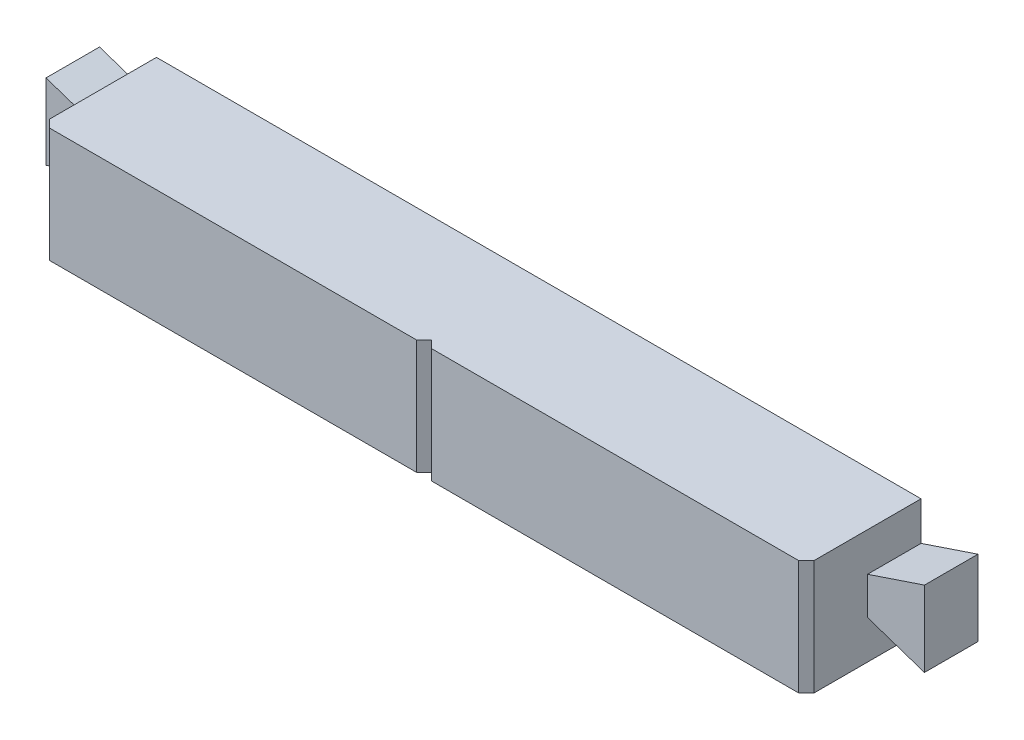
SolidWorks part; units mm, degrees
ref_plane "Front Plane" through (0, 0, 0) normal (0, 0, 1) x (1, 0, 0)
ref_plane "Top Plane" through (0, 0, 0) normal (0, 1, 0) x (1, 0, 0)
ref_plane "Right Plane" through (0, 0, 0) normal (1, 0, 0) x (0, 0, -1)
sketch "Sketch1" plane through (0, 0, 0) normal (0, 0, 1) x (1, 0, 0)
  line L1 (-50, -7.5) -> (50, -7.5)
  line L2 (-50, -7.5) -> (-50, 7.5)
  line L3 (-50, 7.5) -> (50, 7.5)
  line L4 (50, -7.5) -> (50, 7.5)
  line L5 (-50, -7.5) -> (50, 7.5) construction
  line L6 (-50, 7.5) -> (50, -7.5) construction
  point P0 (0, 0)
  dimension "D1" = 100
  dimension "D2" = 15
extrude "Body" add sketch "Sketch1" along normal blind 15
sketch "Sketch2" plane through (0, 0, 0) normal (0, 0, 1) x (1, 0, 0)
  line L0 (-50, 0) -> (50, 0) construction
  line L1 (-50, 7.5) -> (-50, -7.5) construction
  line L2 (50, -7.5) -> (50, 7.5) construction
  line L3 (-50, 0) -> (-50, 2.45)
  line L4 (-50, 2.45) -> (-57.45, 4.95)
  line L6 (-57.45, -4.95) -> (-50, -2.45)
  line L7 (-50, -2.45) -> (-50, 0)
  line L8 (-50, 0) -> (-63.3586, 0) construction
  line L9 (-57.45, 4.95) -> (-57.45, 0)
  line L10 (-57.45, 0) -> (-57.45, -4.95)
  line L11 (0, 7.5) -> (0, -7.5) construction
  line L12 (50, 7.5) -> (-50, 7.5) construction
  line L13 (-50, -7.5) -> (50, -7.5) construction
  line L14 (50, 0) -> (63.3586, 0) construction
  line L15 (57.45, 0) -> (57.45, -4.95)
  line L16 (57.45, 4.95) -> (57.45, 0)
  line L17 (50, -2.45) -> (50, 0)
  line L18 (57.45, -4.95) -> (50, -2.45)
  line L19 (50, 2.45) -> (57.45, 4.95)
  line L20 (50, 0) -> (50, 2.45)
  dimension "D1" = 2.45
  dimension "D2" = 2.45
  dimension "D3" = 4.95
  dimension "D4" = 4.95
  dimension "D5" = 7.45
extrude "Click" add sketch "Sketch2" along normal blind 7
chamfer "Click Chamfer" distance 1 angle 45 2 edges at (-50, 0, 15) (50, 0, 15)
sketch "Sketch3" plane through (0, -7.5, 0) normal (0, -1, 0) x (1, 0, 0)
  line L0 (-50, 5.75) -> (50, 5.75) construction
  line L1 (-50, 7) -> (-50, 0) construction
  line L2 (50, 14) -> (50, 0) construction
  line L3 (-50, 0) -> (50, 0) construction
  line L4 (0, 15) -> (0, 0) construction
  line L5 (-49, 15) -> (49, 15) construction
  circle A0 centre (-25, 5.75) radius 2.5
  circle A1 centre (25, 5.75) radius 2.5
  dimension "D2" = 5
  dimension "D3" = 5
  dimension "D1" = 5.75
  dimension "D4" = 25
  dimension "D5" = 25
extrude "LED Hole" cut sketch "Sketch3" against normal blind 8
sketch "Sketch4" plane through (0, 0, 15) normal (0, 0, 1) x (1, 0, 0)
  line L0 (0, 7.5) -> (0, -7.5) construction
  line L1 (49, 7.5) -> (-49, 7.5) construction
  line L2 (-49, -7.5) -> (49, -7.5) construction
  line L4 (-1, -7.5) -> (1, -7.5)
  line L5 (-1, -7.5) -> (-1, 7.5)
  line L6 (-1, 7.5) -> (1, 7.5)
  line L7 (1, -7.5) -> (1, 7.5)
  line L8 (-1, -7.5) -> (1, 7.5) construction
  line L9 (-1, 7.5) -> (1, -7.5) construction
  point P6 (0, 0)
  dimension "D1" = 2
extrude "FieldMark" cut sketch "Sketch4" against normal blind 2
chamfer "FieldMark Chamfer" distance 2 angle 45 2 edges at (1, 0, 13) (-1, 0, 13)
ref_plane "Plane1" through (0, -6.5, 0) normal (0, -1, 0) x (-1, 0, 0)
sketch "Sketch6" plane through (0, -7.5, 0) normal (0, -1, 0) x (1, 0, 0)
  line L0 (-25, 5.75) -> (25, 5.75) construction
  line L1 (-25, 5.75) -> (-42.5109, 5.75) construction
  line L2 (25, 5.75) -> (43.3201, 5.75) construction
  line L4 (34.5, -1.75) -> (35.5, -1.75)
  line L5 (34.5, -1.75) -> (34.5, 13.25)
  line L6 (34.5, 13.25) -> (35.5, 13.25)
  line L7 (35.5, -1.75) -> (35.5, 13.25)
  line L8 (34.5, -1.75) -> (35.5, 13.25) construction
  line L9 (34.5, 13.25) -> (35.5, -1.75) construction
  line L10 (14.5, -1.75) -> (15.5, -1.75)
  line L11 (14.5, -1.75) -> (14.5, 13.25)
  line L12 (14.5, 13.25) -> (15.5, 13.25)
  line L13 (15.5, -1.75) -> (15.5, 13.25)
  line L14 (14.5, -1.75) -> (15.5, 13.25) construction
  line L15 (14.5, 13.25) -> (15.5, -1.75) construction
  line L16 (-15.5, -1.75) -> (-14.5, -1.75)
  line L17 (-15.5, -1.75) -> (-15.5, 13.25)
  line L18 (-15.5, 13.25) -> (-14.5, 13.25)
  line L19 (-14.5, -1.75) -> (-14.5, 13.25)
  line L20 (-15.5, -1.75) -> (-14.5, 13.25) construction
  line L21 (-15.5, 13.25) -> (-14.5, -1.75) construction
  line L22 (-35.5, -1.75) -> (-34.5, -1.75)
  line L23 (-35.5, -1.75) -> (-35.5, 13.25)
  line L24 (-35.5, 13.25) -> (-34.5, 13.25)
  line L25 (-34.5, -1.75) -> (-34.5, 13.25)
  line L26 (-35.5, -1.75) -> (-34.5, 13.25) construction
  line L27 (-35.5, 13.25) -> (-34.5, -1.75) construction
  point P4 (35, 5.75)
  point P11 (15, 5.75)
  point P16 (-15, 5.75)
  point P21 (-35, 5.75)
  dimension "D1" = 1
  dimension "D2" = 1
  dimension "D3" = 10
  dimension "D4" = 10
  dimension "D5" = 10
  dimension "D6" = 1
  dimension "D7" = 1
  dimension "D8" = 10
  dimension "D9" = 15
  dimension "D10" = 15
  dimension "D11" = 15
  dimension "D12" = 15
extrude "Light Guide" cut sketch "Sketch6" against normal blind 13 from surface starting at plane "Plane1"
sketch "Sketch7" plane through (0, 0, 0) normal (0, 0, -1) x (-1, 0, 0)
  line L0 (34.5, 6.5) -> (34.5, -6.5) construction
  line L1 (15.5, 6.5) -> (34.5, 6.5)
  line L2 (15.5, 6.5) -> (15.5, 5.5)
  line L3 (15.5, 5.5) -> (34.5, 5.5)
  line L4 (34.5, 6.5) -> (34.5, 5.5)
  line L5 (-15.5, 6.5) -> (-15.5, -6.5) construction
  line L6 (-34.5, 6.5) -> (-15.5, 6.5)
  line L7 (-34.5, 6.5) -> (-34.5, 5.5)
  line L8 (-34.5, 5.5) -> (-15.5, 5.5)
  line L9 (-15.5, 6.5) -> (-15.5, 5.5)
  dimension "D1" = 1
  dimension "D2" = 1
extrude "Cut-Extrude1" cut sketch "Sketch7" against normal blind 13.25
